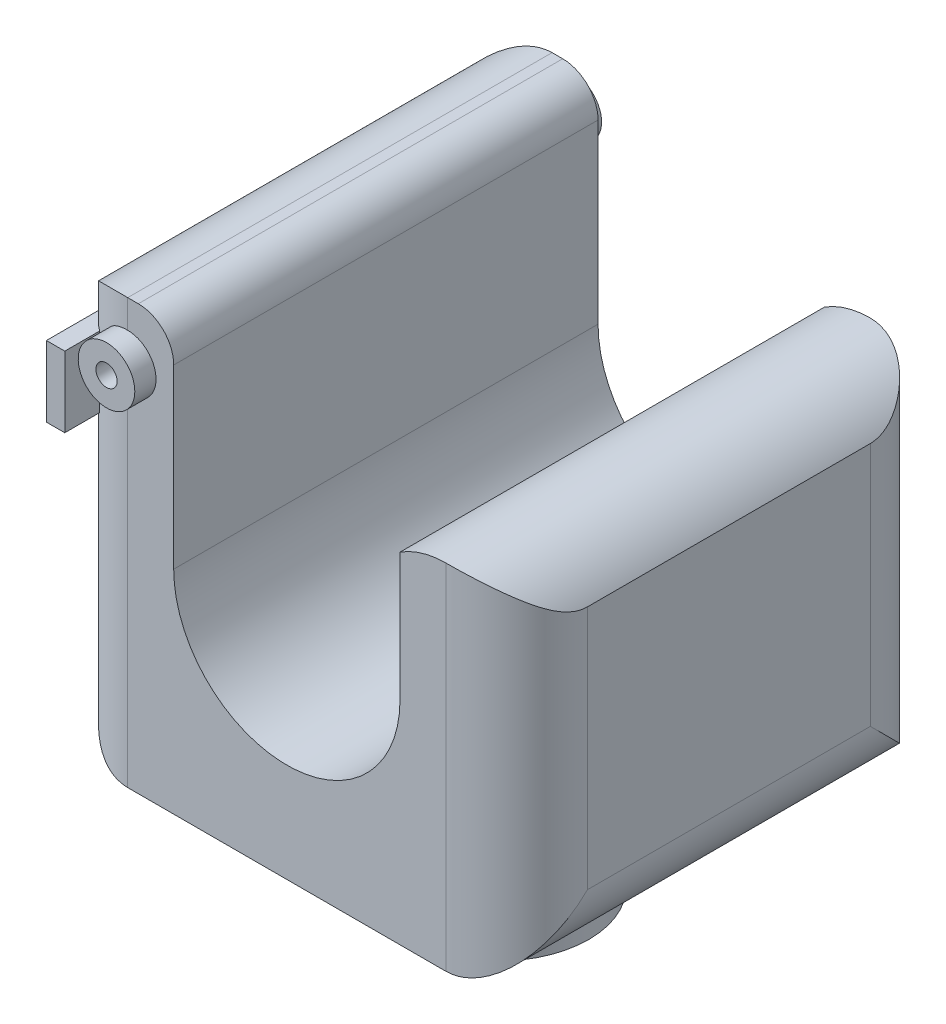
SolidWorks part; units mm, degrees
ref_plane "Alzado" through (0, 0, 0) normal (0, 0, 1) x (1, 0, 0)
ref_plane "Planta" through (0, 0, 0) normal (0, 1, 0) x (1, 0, 0)
ref_plane "Vista lateral" through (0, 0, 0) normal (1, 0, 0) x (0, 0, -1)
sketch "Croquis1" plane through (0, 0, 0) normal (0, 0, 1) x (1, 0, 0)
  line L0 (0, 35.1787) -> (0, -42.6256) construction
  line L1 (-32.5, 30) -> (-16, 30)
  line L2 (-32.5, 30) -> (-32.5, -30)
  line L3 (-32.5, -30) -> (32.5, -30)
  line L4 (32.5, 30) -> (32.5, -30)
  line L5 (-16, 0) -> (-16, 30)
  line L6 (16, 0) -> (16, 30)
  line L7 (16, 30) -> (32.5, 30)
  arc A0 (-16, 0) -> (16, 0) centre (0, 0) ccw
  dimension "D1" = 32
  dimension "D2" = 30
  dimension "D3" = 60
  dimension "D4" = 65
extrude "Saliente-Extruir1" add sketch "Croquis1" along normal mid plane 60
sketch "Croquis2" plane through (0, 0, 30) normal (0, 0, 1) x (1, 0, 0)
  line L0 (-32.5, 30) -> (-32.5, -30) construction
  line L1 (-31, 22) -> (-28.4, 22)
  line L2 (-31, 22) -> (-31, 12)
  line L3 (-31, 12) -> (-28.4, 12)
  line L4 (-28.4, 22) -> (-28.4, 12)
  line L5 (-35.3765, 22) -> (-4.0086, 22) construction
  line L6 (-16, 30) -> (-32.5, 30) construction
  circle A0 centre (0, 0) radius 16 construction
  circle A1 centre (-22.5, 22) radius 1.5
  circle A2 centre (-22.5, 22) radius 4
  dimension "D4" = 3
  dimension "D5" = 8
  dimension "D8" = 32
  dimension "D1" = 2.6
  dimension "D2" = 10
  dimension "D3" = 1.5
  dimension "D6" = 10
  dimension "D7" = 8
extrude "Saliente-Extruir2" add sketch "Croquis2" along normal blind 3
sketch "Croquis4" plane through (0, 0, 0) normal (0, 0, 1) x (1, 0, 0)
  line L0 (0, -19.5054) -> (0, -44.3955) construction
  line L1 (0, -30) -> (14, -30)
  line L2 (-32.5, -30) -> (32.5, -30) construction
  line L3 (14, -30) -> (14, -38)
  line L4 (14, -38) -> (7.3, -38)
  line L5 (7.3, -38) -> (7.3, -42)
  line L6 (7.3, -42) -> (12.7, -42)
  line L7 (12.7, -42) -> (12.7, -46)
  line L8 (12.7, -46) -> (0, -46)
  line L9 (0, -46) -> (0, -30)
  dimension "D1" = 8
  dimension "D2" = 4
  dimension "D3" = 4
  dimension "D4" = 14
  dimension "D5" = 12.7
  dimension "D6" = 5.4
revolve "Revolución1" add sketch "Croquis4" angle 360 about L0
mirror "Simetría2" about plane through (0, 0, 0) normal (0, 0, 1) of "Saliente-Extruir2"
fillet "Redondeo1" radius 10 8 edges at (-32.5, 30, 0) (-32.5, 0, 30) (-32.5, -30, 0) (-32.5, 0, -30) (32.5, -30, 0) (32.5, 0, 30) (32.5, 30, 0) (32.5, 0, -30)
fillet "Redondeo2" radius 5 2 edges at (16, 30, 0) (-16, 30, 0)
sketch "Croquis5" plane through (0, 0, 0) normal (0, 0, 1) x (1, 0, 0)
  line L0 (16, 25) -> (16, 0) construction
  line L1 (32.5, 20) -> (32.5, -20) construction
  line L2 (22.5, -30) -> (22.5, 30) construction
  line L3 (45.8347, 0) -> (-6.8057, 0) construction
  line L4 (32.5, -20) -> (32.5, 20) construction
  line L5 (22.5, 30) -> (21, 30) construction
  line L6 (-16, 0) -> (-16, 25) construction
  line L7 (-21, 30) -> (-22.5, 30) construction
  line L8 (-22.5, 30) -> (-22.5, 26) construction
  line L9 (-22.5, 18) -> (-22.5, -30) construction
  line L10 (-22.5, -30) -> (22.5, -30) construction
  line L11 (32.5, -20) -> (32.5, 20)
  line L12 (22.5, 30) -> (21, 30)
  line L13 (16, 25) -> (16, 0)
  line L14 (-16, 0) -> (-16, 25)
  line L15 (-21, 30) -> (-22.5, 30)
  line L16 (-22.5, 30) -> (-22.5, 26)
  line L17 (-22.5, 18) -> (-22.5, -30)
  line L18 (-22.5, -30) -> (22.5, -30)
  arc A0 (16, 18.0871) -> (32.5, 14.6332) centre (22.5, 8) cw
  arc A1 (32.5, 20) -> (22.5, 30) centre (22.5, 20) ccw construction
  arc A2 (22.5, -30) -> (32.5, -20) centre (22.5, -20) ccw construction
  arc A3 (21, 30) -> (16, 25) centre (21, 25) ccw construction
  arc A4 (-16, 0) -> (16, 0) centre (0, 0) ccw construction
  arc A5 (-16, 25) -> (-21, 30) centre (-21, 25) ccw construction
  arc A6 (-22.5, 18) -> (-22.5, 26) centre (-22.5, 22) ccw construction
  arc A7 (32.5, 20) -> (22.5, 30) centre (22.5, 20) ccw
  arc A8 (22.5, -30) -> (32.5, -20) centre (22.5, -20) ccw
  arc A9 (21, 30) -> (16, 25) centre (21, 25) ccw
  arc A10 (-16, 0) -> (16, 0) centre (0, 0) ccw
  arc A11 (-16, 25) -> (-21, 30) centre (-21, 25) ccw
  arc A12 (-22.5, 18) -> (-22.5, 26) centre (-22.5, 22) ccw
  dimension "D1" = 12
  dimension "D2" = 8
extrude "Cortar-Extruir1" cut sketch "Croquis5" against normal mid plane 100 contours L12 A9 L13 A0 L11 A7 region at (24.0981, 23.6956, 0)
